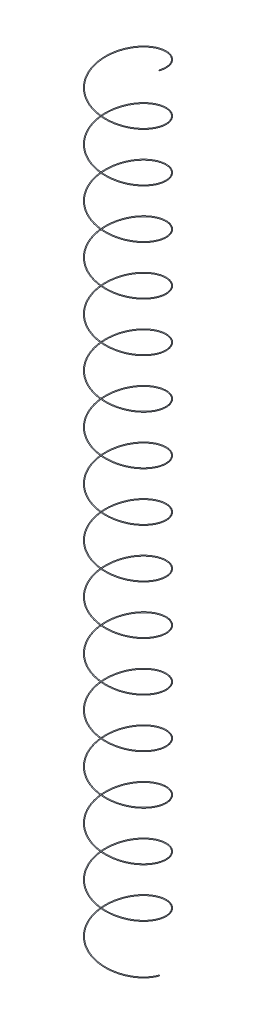
SolidWorks part; units mm, degrees
note: '?' marks a value the reader was unsure of.
ref_plane "Front Plane" through (0, 0, 0) normal (0, 0, 1) x (1, 0, 0)
ref_plane "Top Plane" through (0, 0, 0) normal (0, 1, 0) x (1, 0, 0)
ref_plane "Right Plane" through (0, 0, 0) normal (1, 0, 0) x (0, 0, -1)
sketch "Sketch1" plane through (0, 0, 0) normal (0, 1, 0) x (1, 0, 0)
  circle A0 centre (0, 0) radius 19.9
  dimension "D1" = 39.8
curve "Helix/Spiral1" pitch 31.3 height 500.8 turns 16
sketch "Sketch2" plane through (0, 0, 0) normal (0, 0, 1) x (1, 0, 0)
  circle A0 centre (19.9, 0) radius 0.25
  dimension "D1" = 0.5
sweep "Sweep1" add profiles "Sketch2" path "Helix/Spiral1"
ref_axis "Axis1" through (0, 0, 0) along (0, 1, 0)?
